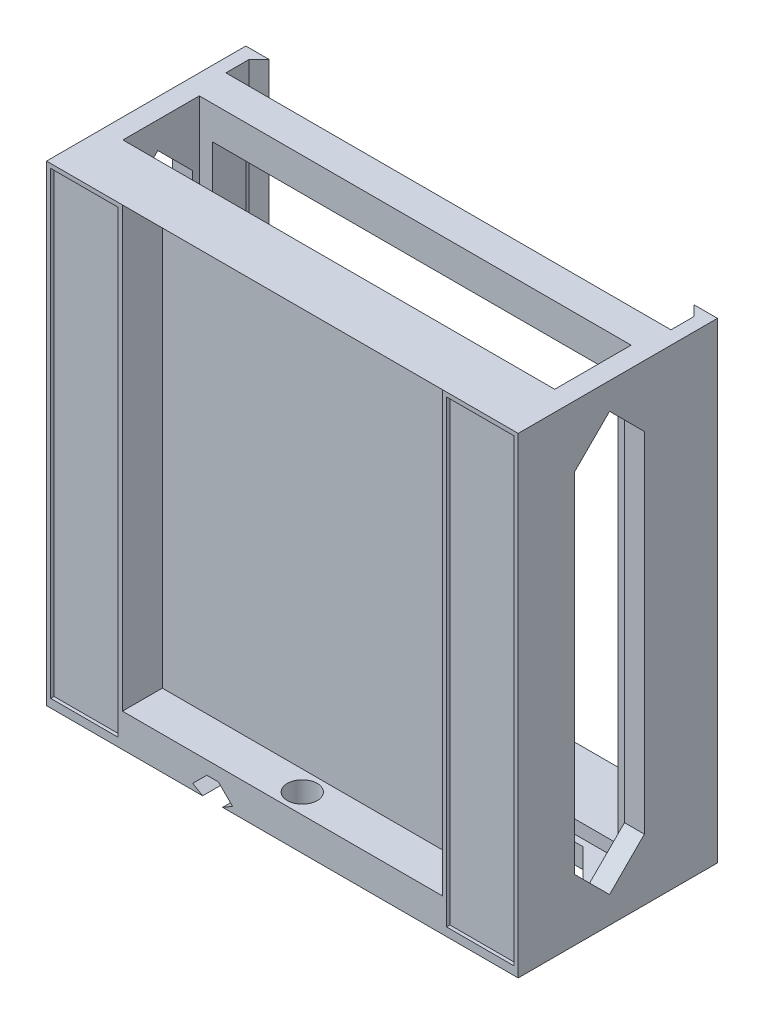
SolidWorks part; units mm, degrees
ref_plane "Front Plane" through (0, 0, 0) normal (1, 0, 0) x (0, 1, 0)
ref_plane "Top Plane" through (0, 0, 0) normal (0, 0, 1) x (0, 1, 0)
ref_plane "Right Plane" through (0, 0, 0) normal (0, 1, 0) x (-1, 0, 0)
sketch "Sketch1" plane through (0, 0, 0) normal (0, 0, 1) x (0, 1, 0)
  line L0 (-71, -71) -> (-71, 71)
  line L1 (-61, -61) -> (61, -61)
  line L2 (-61, -61) -> (-61, 61)
  line L3 (-61, 61) -> (61, 61)
  line L4 (61, -61) -> (61, 61)
  line L5 (-61, -61) -> (61, 61) construction
  line L6 (-61, 61) -> (61, -61) construction
  line L7 (-71, 71) -> (71, 71)
  line L8 (71, -71) -> (71, 71)
  line L9 (-71, -71) -> (71, -71)
  point P0 (0, 0)
  dimension "D1" = 122
  dimension "D2" = 122
  dimension "D3" = 10
extrude "Boss-Extrude1" add sketch "Sketch1" along normal blind 10
sketch "Sketch2" plane through (0, 0, 0) normal (0, 0, -1) x (1, 0, 0)
  line L1 (-71, 71) -> (71, 71)
  line L2 (71, 71) -> (71, 61)
  line L3 (71, 71) -> (71, -71) construction
  line L4 (71, 61) -> (-71, 61)
  line L5 (-71, -71) -> (-71, 71) construction
  line L6 (-71, 61) -> (-71, 71)
  line L7 (-61, 61) -> (61, 61) construction
extrude "Boss-Extrude2" add sketch "Sketch2" along normal blind 10
sketch "Sketch3" plane through (0, -61, 0) normal (0, 1, 0) x (-1, 0, 0)
  line L3 (-67, -7) -> (-64, -10)
  line L4 (71, -10) -> (-71, -10) construction
  line L5 (-64, -10) -> (-71, -10)
  line L6 (-71, -10) -> (-71, 0)
  line L7 (0, 11) -> (0, -11) construction
  line L8 (64, -10) -> (71, -10)
  line L9 (67, -7) -> (64, -10)
  line L10 (67, 0) -> (67, -7)
  line L11 (71, 0) -> (67, 0)
  line L12 (71, -10) -> (71, 0)
  line L13 (-71, 0) -> (-67, 0)
  line L14 (-61, 0) -> (-71, 0) construction
  line L15 (-67, 0) -> (-67, -7)
  dimension "D1" = 4
  dimension "D2" = 45
  dimension "D3" = 7
extrude "Boss-Extrude3" add sketch "Sketch3" along normal up to surface (132 mm away) up to face at (0, 71, 5)
sketch "Sketch4" plane through (0, 0, 10) normal (0, 0, 1) x (1, 0, 0)
  line L1 (-60, -60) -> (60, -60) construction
  line L2 (-60, -60) -> (-60, 60) construction
  line L3 (-60, 60) -> (60, 60) construction
  line L4 (60, -60) -> (60, 60) construction
  line L5 (-60, -60) -> (60, 60) construction
  line L6 (-60, 60) -> (60, -60) construction
  point P0 (0, 0)
  dimension "D1" = 120
  dimension "D2" = 120
sketch "Sketch5" plane through (0, 0, 10) normal (0, 0, 1) x (1, 0, 0)
  line L0 (71, -71) -> (71, 71) construction
  line L1 (-65, -65) -> (65, -65)
  line L2 (-65, -65) -> (-65, 65)
  line L4 (65, -65) -> (65, 65)
  line L5 (-65, -65) -> (65, 65) construction
  line L6 (-65, 65) -> (65, -65) construction
  line L7 (-71, 71) -> (-65, 71)
  line L8 (71, 71) -> (-71, 71) construction
  line L9 (-65, 71) -> (-65, 65)
  line L10 (-71, 71) -> (-71, -71)
  line L11 (-71, -71) -> (71, -71)
  line L12 (71, -71) -> (71, 65)
  line L13 (71, 65) -> (71, 71)
  line L14 (71, 71) -> (65, 71)
  line L15 (65, 71) -> (65, 65)
  point P1 (0, 0)
  dimension "D1" = 6
extrude "Boss-Extrude4" add sketch "Sketch5" along normal blind 2
sketch "Sketch6" plane through (0, 0, 12) normal (0, 0, 1) x (1, 0, 0)
  line L0 (-65, -65) -> (-65, 71) construction
  line L1 (-71, 71) -> (-65, 71)
  line L2 (-71, 71) -> (-71, 63)
  line L3 (-71, 63) -> (-65, 63)
  line L4 (-65, 71) -> (-65, 63)
  line L10 (-65, -65) -> (-65, -63)
  line L11 (-65, -63) -> (-71, -63)
  line L12 (-71, 71) -> (-71, -71) construction
  line L13 (-71, -63) -> (-71, -71)
  line L14 (-71, -71) -> (-63, -71)
  line L15 (-71, -71) -> (71, -71) construction
  line L16 (-63, -71) -> (-63, -65)
  line L17 (65, -65) -> (-65, -65) construction
  line L18 (-63, -65) -> (-65, -65)
  line L19 (0, -12.1) -> (0, 12.1) construction
  line L20 (63, -71) -> (63, -65)
  line L21 (71, -71) -> (63, -71)
  line L22 (71, -63) -> (71, -71)
  line L23 (65, -63) -> (71, -63)
  line L24 (65, -65) -> (65, -63)
  line L25 (63, -65) -> (65, -65)
  line L26 (71, 63) -> (65, 63)
  line L27 (65, 71) -> (65, 63)
  line L28 (71, 71) -> (65, 71)
  line L29 (71, 71) -> (71, 63)
  dimension "D1" = 8
  dimension "D3" = 8
  dimension "D4" = 8
extrude "Boss-Extrude5" add sketch "Sketch6" along normal blind 21
sketch "Sketch7" plane through (0, -71, 0) normal (0, -1, 0) x (1, 0, 0)
  line L0 (-63, 33) -> (63, 33)
  line L1 (63, 33) -> (71, 33)
  line L2 (71, 33) -> (71, 38)
  line L3 (71, 38) -> (-71, 38)
  line L4 (-71, 38) -> (-71, 33)
  line L5 (-71, 33) -> (-63, 33)
  dimension "D1" = 5
extrude "Boss-Extrude6" add sketch "Sketch7" against normal up to surface (142 mm away) up to face at (0, 71, 7)
sketch "Sketch8" plane through (71, 0, 0) normal (1, 0, 0) x (0, 1, 0)
  line L0 (63, 22.5) -> (52.5, 33)
  line L1 (63, 33) -> (63, 12) construction
  line L2 (63, 33) -> (-63, 33) construction
  line L3 (52.5, 33) -> (63, 33)
  line L4 (63, 33) -> (63, 22.5)
  line L5 (63, 22.5) -> (52.5, 12)
  line L6 (-63, 12) -> (63, 12) construction
  line L7 (52.5, 12) -> (63, 12)
  line L8 (63, 12) -> (63, 22.5)
  line M8 (-63, 33) -> (63, 33)
  line M9 (63, 33) -> (63, 12)
  line M10 (63, 12) -> (-63, 12)
  dimension "D1" = 45
extrude "Boss-Extrude7" add sketch "Sketch8" against normal up to surface (6 mm away) contours L5 M9 M10 | L0 M9 M8 region at (71, 59.5, 29.5) region at (71, 59.5, 15.5) up to face at (65, 1.5, 22)
sketch "Sketch9" plane through (-71, 0, 0) normal (-1, 0, 0) x (0, -1, 0)
  line L0 (-63, 33) -> (-52.5, 33)
  line L1 (-52.5, 33) -> (-63, 22.5)
  line L2 (-63, 22.5) -> (-63, 33)
  line L3 (-63, 22.5) -> (-63, 12)
  line L4 (-63, 12) -> (-52.5, 12)
  line L5 (-52.5, 12) -> (-63, 22.5)
  line M8 (-63, 33) -> (63, 33)
  line M10 (63, 12) -> (-63, 12)
  line M11 (-63, 12) -> (-63, 33)
extrude "Boss-Extrude8" add sketch "Sketch9" against normal up to surface (6 mm away) contours L5 M10 M11 | L1 M8 M11 region at (-71, 59.5, 15.5) region at (-71, 59.5, 29.5) up to face at (-65, 1.5, 22)
mirror "Mirror4" about plane through (0, 0, 0) normal (0, 1, 0) of "Boss-Extrude8", "Boss-Extrude7"
sketch "Sketch10" plane through (0, 0, 38) normal (0, 0, 1) x (1, 0, 0)
  line L0 (-48.14, 59) -> (-48.14, -48.14)
  line L2 (48.14, -48.14) -> (48.14, 59)
  line L4 (71, 71) -> (-71, 71)
  line L5 (-71, 71) -> (-71, -71)
  line L6 (-71, -71) -> (71, -71)
  line L7 (71, -71) -> (71, 71)
  line L9 (-71, 71) -> (-71, -71)
  line L10 (-71, -71) -> (71, -71)
  line L11 (71, -71) -> (71, 71)
  line L13 (-48.14, 48.14) -> (-48.14, -48.14) construction
  line L14 (48.14, -48.14) -> (48.14, 48.14) construction
  line L15 (-71, 71) -> (71, 71)
  line L16 (48.14, 48.14) -> (-48.14, 48.14) construction
  line L17 (-48.14, 59) -> (48.14, 59)
  line L19 (-48.14, -48.14) -> (-48.14, -61)
  line L20 (-48.14, -48.14) -> (48.14, -48.14) construction
  line L21 (71, 71) -> (-71, 71) construction
  line L22 (-48.14, -61) -> (48.14, -61)
  line L23 (48.14, -61) -> (48.14, -48.14)
  dimension "D3" = 12
  dimension "D4" = 10
  dimension "D1" = 0
  dimension "D2" = 22.86
extrude "Boss-Extrude9" add sketch "Sketch10" along normal blind 12
sketch "Sketch11" plane through (0, -71, 0) normal (0, -1, 0) x (1, 0, 0)
  line L0 (-63, 22.5) -> (-52.5, 12)
  line L1 (-63, 33) -> (-63, 12) construction
  line L2 (-63, 12) -> (63, 12) construction
  line L3 (-52.5, 12) -> (-63, 12)
  line L4 (-63, 22.5) -> (-63, 12)
  line L5 (-63, 22.5) -> (-63, 33)
  line L6 (-63, 33) -> (-52.5, 33)
  line L7 (-63, 33) -> (63, 33) construction
  line L8 (-52.5, 33) -> (-63, 22.5)
  point P13 (0, 0)
  dimension "D1" = 45
extrude "Boss-Extrude14" add sketch "Sketch11" against normal up to surface (6 mm away) contours L0 | L6 region at (-59.5, -71, 15.5) region at (-59.5, -71, 29.5) up to face at (0, -65, 22)
mirror "Mirror5" about plane through (0, 0, 0) normal (1, 0, 0) of "Boss-Extrude14"
sketch "Sketch13" plane through (0, -61, 0) normal (0, 1, 0) x (-1, 0, 0)
  line L0 (0, 50) -> (0, 38) construction
  line L1 (48.14, 50) -> (-48.14, 50) construction
  line L2 (48.14, 38) -> (-48.14, 38) construction
  circle A0 centre (0, 44) radius 4.5
  dimension "D1" = 9
extrude "Cut-Extrude2" cut sketch "Sketch13" against normal through all
sketch "Sketch14" plane through (0, 0, 50) normal (0, 0, 1) x (1, 0, 0)
  line L0 (71, 71) -> (-71, 71) construction
  line L1 (-49.41, 69.73) -> (-69.73, 69.73)
  line L2 (-49.41, 69.73) -> (-49.41, -68.46)
  line L3 (-49.41, -68.46) -> (-69.73, -68.46)
  line L4 (-69.73, 69.73) -> (-69.73, -68.46)
  line L5 (-71, 71) -> (-71, -71) construction
  line L7 (-71, -71) -> (71, -71) construction
  line L8 (0, -33) -> (0, 33) construction
  line L9 (49.41, -68.46) -> (69.73, -68.46)
  line L10 (69.73, 69.73) -> (69.73, -68.46)
  line L11 (49.41, 69.73) -> (69.73, 69.73)
  line L12 (49.41, 69.73) -> (49.41, -68.46)
  dimension "D1" = 1.27
  dimension "D2" = 1.27
  dimension "D3" = 20.32
  dimension "D4" = 2.54
extrude "Cut-Extrude3" cut sketch "Sketch14" against normal blind 1
chamfer "Chamfer4" distance 12 angle 45 1 edges at (0, 59, 50)
sketch "Sketch15" plane through (0, 0, 50) normal (0, 0, 1) x (1, 0, 0)
  line L0 (-24, -71) -> (-18, -71)
  line L1 (-71, -71) -> (71, -71) construction
  line L2 (-18, -71) -> (-15, -69.2549)
  line L3 (-15, -69.2549) -> (-19.2549, -65)
  line L4 (-19.2549, -65) -> (-22.7451, -65)
  line L5 (-22.7451, -65) -> (-27, -69.2549)
  line L6 (-27, -69.2549) -> (-24, -71)
  line L7 (0, -71) -> (0, -61) construction
  line L8 (-48.14, -61) -> (48.14, -61) construction
  point P4 (-21, -71)
  point P9 (-21, -65)
  dimension "D1" = 45
  dimension "D2" = 45
  dimension "D3" = 6
  dimension "D4" = 6
  dimension "D5" = 15
  dimension "D6" = 12
extrude "Cut-Extrude4" cut sketch "Sketch15" against normal through all
